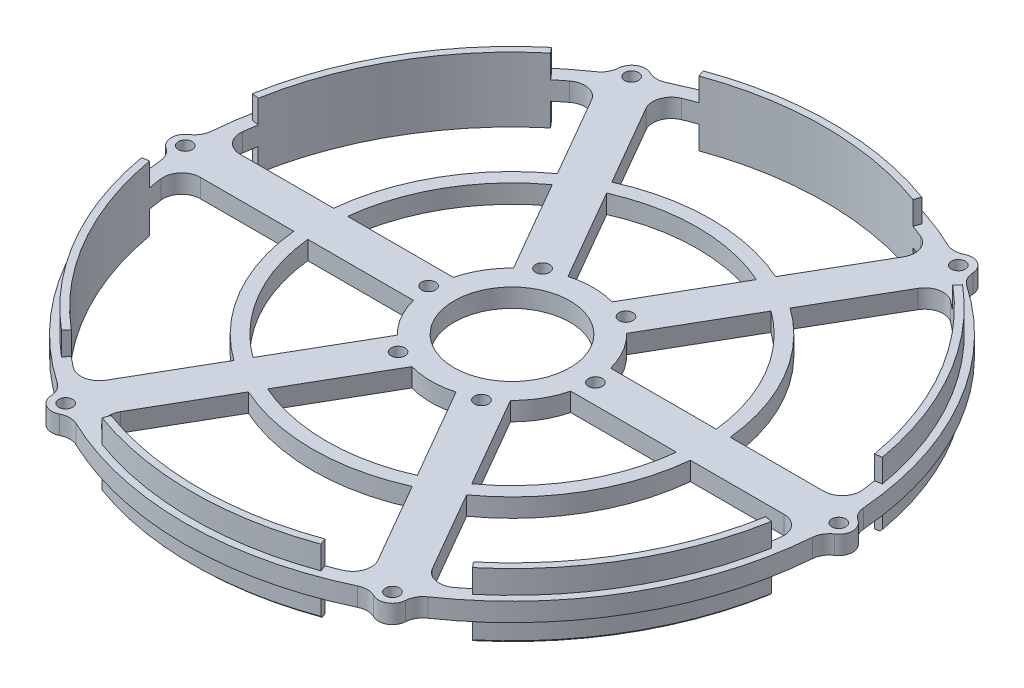
SolidWorks part; units mm, degrees
ref_plane "前视基准面" through (0, 0, 0) normal (0, 0, 1) x (1, 0, 0)
ref_plane "上视基准面" through (0, 0, 0) normal (0, 1, 0) x (1, 0, 0)
ref_plane "右视基准面" through (0, 0, 0) normal (1, 0, 0) x (0, 0, -1)
sketch "草图1" plane through (0, 0, 0) normal (0, 1, 0) x (1, 0, 0)
  line L12 (-35.25, -61.0548) -> (0, 0) construction
  line L13 (-67.3629, 4.3002) -> (-9.579, 4.3002)
  line L14 (-67.3629, -4.3002) -> (-9.579, -4.3002)
  line L15 (9.579, 4.3002) -> (67.3629, 4.3002)
  line L16 (9.579, -4.3002) -> (67.3629, -4.3002)
  line L17 (1.0654, -10.4458) -> (29.9573, -60.4881)
  line L18 (8.5136, -6.1456) -> (37.4056, -56.1878)
  line L19 (-29.9573, 60.4881) -> (-1.0654, 10.4458)
  line L20 (-37.4056, 56.1878) -> (-8.5136, 6.1456)
  line L21 (-8.5136, -6.1456) -> (-37.4056, -56.1878)
  line L22 (-1.0654, -10.4458) -> (-29.9573, -60.4881)
  line L23 (37.4056, 56.1878) -> (8.5136, 6.1456)
  line L24 (29.9573, 60.4881) -> (1.0654, 10.4458)
  line L25 (-9.579, 4.3002) -> (-67.3629, 4.3002)
  line L26 (-9.579, -4.3002) -> (-67.3629, -4.3002)
  line L27 (67.3629, -4.3002) -> (9.579, -4.3002)
  line L28 (67.3629, 4.3002) -> (9.579, 4.3002)
  line L29 (-1.0654, 10.4458) -> (-29.9573, 60.4881)
  line L30 (-8.5136, 6.1456) -> (-37.4056, 56.1878)
  line L31 (29.9573, -60.4881) -> (1.0654, -10.4458)
  line L32 (37.4056, -56.1878) -> (8.5136, -6.1456)
  line L33 (8.5136, 6.1456) -> (37.4056, 56.1878)
  line L34 (1.0654, 10.4458) -> (29.9573, 60.4881)
  line L35 (-37.4056, -56.1878) -> (-8.5136, -6.1456)
  line L36 (-29.9573, -60.4881) -> (-1.0654, -10.4458)
  line L37 (10.5, 0) -> (70.5, 0) construction
  line L38 (-10.5, 0) -> (9.5, 0) construction
  arc A0 (-7.8594, 1.4934) -> (-7.8594, -1.4934) centre (0, 0) ccw construction
  circle A1 centre (-8, 0) radius 1.5
  circle A2 centre (0, 8) radius 1.5
  circle A3 centre (8, 0) radius 1.5
  circle A4 centre (0, -8) radius 1.5
  arc A5 (-8.5136, 6.1456) -> (-9.579, 4.3002) centre (0, 0) ccw
  arc A6 (-67.3629, -4.3002) -> (-37.4056, -56.1878) centre (0, 0) ccw
  arc A7 (-70.5, 3) -> (-70.5, -3) centre (-70.5, 0) ccw
  circle A8 centre (-70.5, 0) radius 1.5
  arc A9 (-32.6519, 62.5548) -> (-37.8481, 59.5548) centre (-35.25, 61.0548) ccw
  circle A10 centre (-35.25, 61.0548) radius 1.5
  arc A11 (37.8481, 59.5548) -> (32.6519, 62.5548) centre (35.25, 61.0548) ccw
  circle A12 centre (35.25, 61.0548) radius 1.5
  arc A13 (70.5, -3) -> (70.5, 3) centre (70.5, 0) ccw
  circle A14 centre (70.5, 0) radius 1.5
  arc A15 (32.6519, -62.5548) -> (37.8481, -59.5548) centre (35.25, -61.0548) ccw
  circle A16 centre (35.25, -61.0548) radius 1.5
  arc A17 (-37.8481, -59.5548) -> (-32.6519, -62.5548) centre (-35.25, -61.0548) ccw
  circle A18 centre (-35.25, -61.0548) radius 1.5
  arc A21 (1.4934, 7.8594) -> (-6.746, 4.3002) centre (0, 0) ccw construction
  arc A22 (-1.4934, -7.8594) -> (1.4934, -7.8594) centre (0, 0) ccw construction
  arc A23 (7.8594, -1.4934) -> (6.746, 4.3002) centre (0, 0) ccw construction
  circle A24 centre (0, 0) radius 4.5
  arc A25 (1.0654, 10.4458) -> (-1.0654, 10.4458) centre (0, 0) ccw
  arc A26 (9.579, 4.3002) -> (8.5136, 6.1456) centre (0, 0) ccw
  arc A27 (8.5136, -6.1456) -> (9.579, -4.3002) centre (0, 0) ccw
  arc A28 (-1.0654, -10.4458) -> (1.0654, -10.4458) centre (0, 0) ccw
  arc A29 (-9.579, -4.3002) -> (-8.5136, -6.1456) centre (0, 0) ccw
  arc A30 (-37.4056, 56.1878) -> (-67.3629, 4.3002) centre (0, 0) ccw
  arc A31 (29.9573, 60.4881) -> (-29.9573, 60.4881) centre (0, 0) ccw
  arc A32 (67.3629, 4.3002) -> (37.4056, 56.1878) centre (0, 0) ccw
  arc A33 (37.4056, -56.1878) -> (67.3629, -4.3002) centre (0, 0) ccw
  arc A34 (-29.9573, -60.4881) -> (29.9573, -60.4881) centre (0, 0) ccw
  arc A35 (32.6519, 62.5548) -> (-32.6519, 62.5548) centre (0, 0) ccw
  arc A36 (70.5, 3) -> (37.8481, 59.5548) centre (0, 0) ccw
  arc A37 (37.8481, -59.5548) -> (70.5, -3) centre (0, 0) ccw
  arc A38 (-32.6519, -62.5548) -> (32.6519, -62.5548) centre (0, 0) ccw
  arc A39 (-70.5, -3) -> (-37.8481, -59.5548) centre (0, 0) ccw
  arc A40 (-37.8481, 59.5548) -> (-70.5, 3) centre (0, 0) ccw
  point P14 (0, 0)
  point P15 (0, 0)
  point P52 (0, 0)
  point P111 (0, 0)
  point P135 (0, 0)
  dimension "D1" = 16
  dimension "D2" = 3
  dimension "D4" = 2.5
  dimension "D5" = 135
  dimension "D6" = 6
  dimension "D7" = 3
  dimension "D9" = 9
  dimension "D8" = 6
  dimension "D3" = 4
  dimension "D10" = 6
extrude "凸台-拉伸1" add sketch "草图1" along normal blind 4 contours A9 A40 A7 A39 A17 A38 A15 A37 A13 A36 A11 A35 L14 A29 L21 A6 A1 A2 region at (-59.3453, 0, -34.263)
fillet "圆角1" radius 4 24 edges at (-37.4056, 2, 56.1878) (-67.3629, 2, 4.3002) (-70.5, 2, 3) (-70.5, 2, -3) (-67.3629, 2, -4.3002) (-37.4056, 2, -56.1878) (-29.9573, 2, -60.4881) (-37.8481, 2, -59.5548) (-32.6519, 2, -62.5548) (32.6519, 2, -62.5548) (29.9573, 2, -60.4881) (37.4056, 2, -56.1878) (37.8481, 2, -59.5548) (70.5, 2, -3) (70.5, 2, 3) (67.3629, 2, -4.3002) (67.3629, 2, 4.3002) (37.8481, 2, 59.5548) (37.4056, 2, 56.1878) (32.6519, 2, 62.5548) (29.9573, 2, 60.4881) (-37.8481, 2, 59.5548) (-29.9573, 2, 60.4881) (-32.6519, 2, 62.5548)
fillet "圆角2" radius 4 12 edges at (-1.0654, 2, 10.4458) (-8.5136, 2, 6.1456) (-9.579, 2, 4.3002) (-9.579, 2, -4.3002) (-8.5136, 2, -6.1456) (1.0654, 2, -10.4458) (-1.0654, 2, -10.4458) (9.579, 2, -4.3002) (8.5136, 2, -6.1456) (9.579, 2, 4.3002) (8.5136, 2, 6.1456) (1.0654, 2, 10.4458)
sketch "草图2" plane through (0, 0, 0) normal (0, -1, 0) x (-1, 0, 0)
  line L0 (23.0864, -63.4293) -> (23.5994, -64.8388)
  line L1 (0, 0) -> (0, -46.6688) construction
  line L2 (-23.0864, -63.4293) -> (-23.5994, -64.8388)
  line L3 (-43.3882, -51.708) -> (-44.3523, -52.8571)
  line L4 (-66.4745, -11.7213) -> (-67.9517, -11.9817)
  line L5 (-66.4745, 11.7213) -> (-67.9517, 11.9817)
  line L6 (-43.3882, 51.708) -> (-44.3523, 52.8571)
  line L7 (-23.0864, 63.4293) -> (-23.5994, 64.8388)
  line L8 (23.0864, 63.4293) -> (23.5994, 64.8388)
  line L9 (43.3882, 51.708) -> (44.3523, 52.8571)
  line L10 (66.4745, 11.7213) -> (67.9517, 11.9817)
  line L11 (66.4745, -11.7213) -> (67.9517, -11.9817)
  line L12 (43.3882, -51.708) -> (44.3523, -52.8571)
  arc A0 (-23.0864, -63.4293) -> (23.0864, -63.4293) centre (0, 0) ccw
  arc A1 (-23.5994, -64.8388) -> (23.5994, -64.8388) centre (0, 0) ccw
  arc A2 (-66.4745, -11.7213) -> (-43.3882, -51.708) centre (0, 0) ccw
  arc A3 (-67.9517, -11.9817) -> (-44.3523, -52.8571) centre (0, 0) ccw
  arc A4 (-43.3882, 51.708) -> (-66.4745, 11.7213) centre (0, 0) ccw
  arc A5 (-44.3523, 52.8571) -> (-67.9517, 11.9817) centre (0, 0) ccw
  arc A6 (23.0864, 63.4293) -> (-23.0864, 63.4293) centre (0, 0) ccw
  arc A7 (23.5994, 64.8388) -> (-23.5994, 64.8388) centre (0, 0) ccw
  arc A8 (66.4745, 11.7213) -> (43.3882, 51.708) centre (0, 0) ccw
  arc A9 (67.9517, 11.9817) -> (44.3523, 52.8571) centre (0, 0) ccw
  arc A10 (43.3882, -51.708) -> (66.4745, -11.7213) centre (0, 0) ccw
  arc A11 (44.3523, -52.8571) -> (67.9517, -11.9817) centre (0, 0) ccw
  point P30 (0, 0)
  dimension "D1" = 1.5
  dimension "D2" = 20
  dimension "D3" = 6
extrude "凸台-拉伸2" add sketch "草图2" along normal blind 5 and the other way blind 9
chamfer "倒角1" distance 0.5 angle 45 6 edges at (59.7558, -5, -34.5) (59.7558, -5, 34.5) (0, -5, 69) (-59.7558, -5, 34.5) (-59.7558, -5, -34.5) (0, -5, -69)
sketch "草图3" plane through (0, 4, 0) normal (0, 1, 0) x (1, 0, 0)
  circle A0 centre (0, 0) radius 40
  circle A1 centre (0, 0) radius 43
  dimension "D1" = 80
  dimension "D2" = 3
extrude "凸台-拉伸3" add sketch "草图3" against normal up to surface (4 mm away) up to face at (-42.1051, 0, 24.3094)
sketch "草图4" plane through (0, 4, 0) normal (0, 1, 0) x (1, 0, 0)
  circle A0 centre (0, 0) radius 12.5
  dimension "D1" = 25
extrude "切除-拉伸1" cut sketch "草图4" against normal blind 10
sketch "草图5" plane through (0, 4, 0) normal (0, 1, 0) x (1, 0, 0)
  circle A0 centre (0, 0) radius 12.5
  circle A1 centre (0, 0) radius 17.5
  dimension "D1" = 5
extrude "凸台-拉伸4" add sketch "草图5" against normal up to surface (4 mm away) up to face at (0, 0, 58.1881)
sketch "草图6" plane through (0, 0, 0) normal (0, -1, 0) x (1, 0, 0)
  line L0 (0, 0) -> (35.25, 61.0548) construction
  circle A0 centre (9, 15.5885) radius 1.5
  circle A1 centre (18, 0) radius 1.5
  circle A2 centre (9, -15.5885) radius 1.5
  circle A3 centre (-9, -15.5885) radius 1.5
  circle A4 centre (-18, 0) radius 1.5
  circle A5 centre (-9, 15.5885) radius 1.5
  point P18 (0, 0)
  dimension "D1" = 3
  dimension "D2" = 18
  dimension "D3" = 6
extrude "切除-拉伸2" cut sketch "草图6" against normal blind 9
